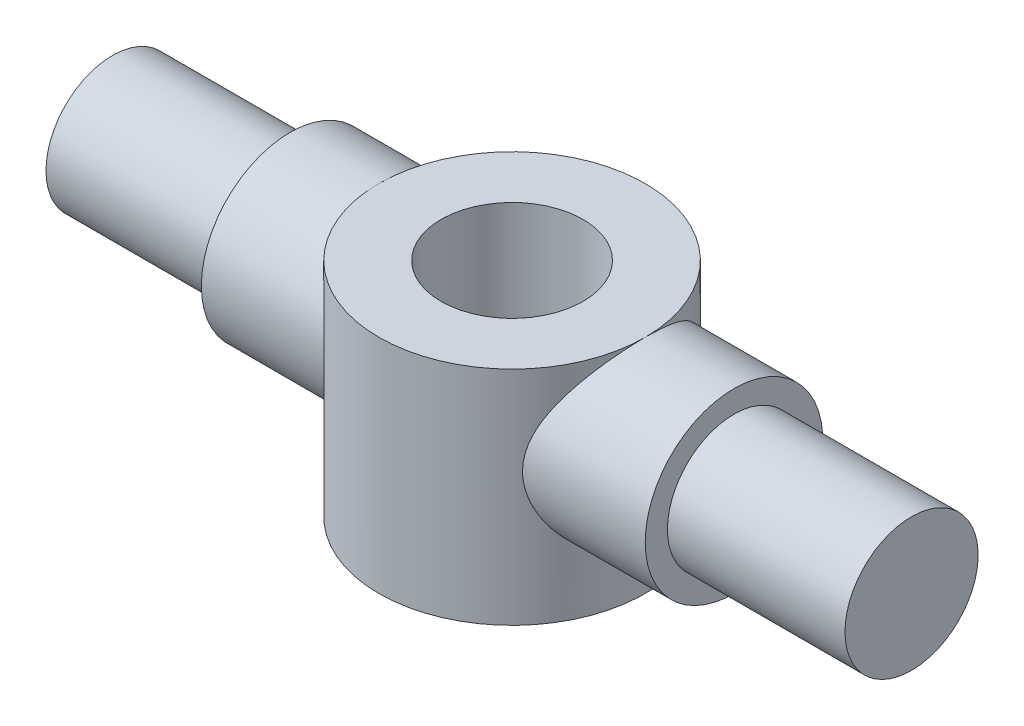
SolidWorks part; units mm, degrees
ref_plane "Front Plane" through (0, 0, 0) normal (0, 0, 1) x (1, 0, 0)
ref_plane "Top Plane" through (0, 0, 0) normal (0, 1, 0) x (1, 0, 0)
ref_plane "Right Plane" through (0, 0, 0) normal (1, 0, 0) x (0, 0, -1)
sketch "Sketch1" plane through (0, 0, 0) normal (0, 1, 0) x (1, 0, 0)
  line L0 (-9, 0) -> (9, 0) construction
  line L1 (-5, -2) -> (-2.2361, -2)
  line L2 (-5, -2) -> (-5, 2) construction
  line L3 (-5, 2) -> (-2.2361, 2) construction
  line L4 (-2.2361, -2) -> (-2.2361, 2) construction
  line L5 (-5, -2) -> (-2.2361, 2) construction
  line L6 (-5, 2) -> (-2.2361, -2) construction
  line L7 (-9, -1.5) -> (-5, -1.5)
  line L8 (-9, -1.5) -> (-9, 1.5) construction
  line L9 (-9, 1.5) -> (-5, 1.5) construction
  line L10 (-5, -1.5) -> (-5, 1.5) construction
  line L11 (-9, -1.5) -> (-5, 1.5) construction
  line L12 (-9, 1.5) -> (-5, -1.5) construction
  line L13 (5, -2) -> (2.2361, -2)
  line L14 (5, -2) -> (5, 2) construction
  line L15 (5, 2) -> (2.2361, 2) construction
  line L16 (2.2361, -2) -> (2.2361, 2) construction
  line L17 (5, -2) -> (2.2361, 2) construction
  line L18 (5, 2) -> (2.2361, -2) construction
  line L19 (9, -1.5) -> (5, -1.5)
  line L20 (9, -1.5) -> (9, 1.5) construction
  line L21 (9, 1.5) -> (5, 1.5) construction
  line L22 (5, -1.5) -> (5, 1.5) construction
  line L23 (9, -1.5) -> (5, 1.5) construction
  line L24 (9, 1.5) -> (5, -1.5) construction
  line L25 (-9, -1.5) -> (-9, 0)
  line L26 (-9, 0) -> (-2.2361, 0)
  line L27 (-2.2361, 0) -> (-2.2361, -2)
  line L28 (-5, -2) -> (-5, -1.5)
  line L29 (5, -2) -> (5, -1.5)
  line L30 (2.2361, -2) -> (2.2361, 0)
  line L31 (2.2361, 0) -> (9, 0)
  line L32 (9, 0) -> (9, -1.5)
  line L33 (9, -1.5) -> (9.0021, -1.4749)
  circle A0 centre (0, 0) radius 3
  circle A1 centre (0, 0) radius 1.6
  arc A2 (-2.2361, 2) -> (2.2361, 2) centre (0, 0) cw
  arc A3 (-2.2361, -2) -> (2.2361, -2) centre (0, 0) ccw
  point P4 (-3.618, 0)
  point P9 (-7, 0)
  point P14 (3.618, 0)
  point P19 (7, 0)
  dimension "D1" = 3.2
  dimension "D2" = 3
  dimension "D3" = 4
  dimension "D4" = 3
  dimension "D5" = 10
  dimension "D6" = 4
revolve "Revolve2" add sketch "Sketch1" angle 360 about L26 region at (-5.6615, 0, 0.8804) region at (-2.5452, 0, 0.7646) region at (5.6615, 0, 0.8804) region at (2.5452, 0, 0.7646)
extrude "Boss-Extrude1" add sketch "Sketch1<5>" along normal blind 2 and the other way blind 3 contours L31 A0 L26 L27 L30 A1 | L30 A0 L31 | L26 A0 L27 region at (-2.5452, 0, 0.7646) region at (-2.1512, 0, 1) region at (2.5452, 0, 0.7646)
sketch "Sketch1<5>" plane through (0, 0, 0) normal (0, 1, 0) x (1, 0, 0) same geometry as "Sketch1"
